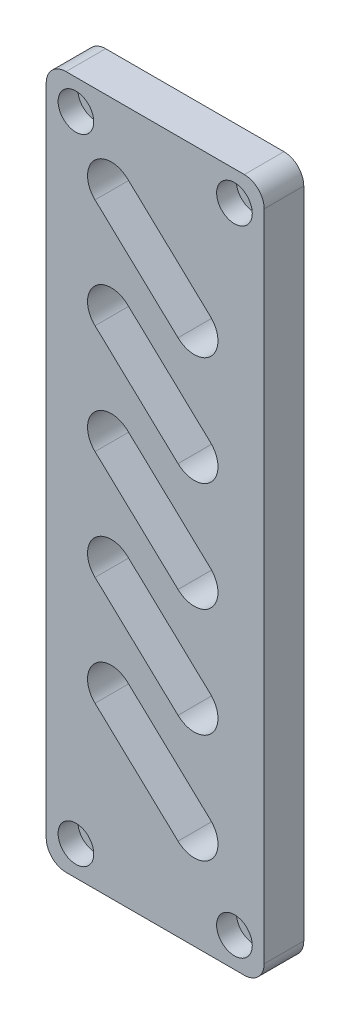
SolidWorks part; units mm, degrees
ref_plane "前视基准面" through (0, 0, 0) normal (0, 0, 1) x (1, 0, 0)
ref_plane "上视基准面" through (0, 0, 0) normal (0, 1, 0) x (1, 0, 0)
ref_plane "右视基准面" through (0, 0, 0) normal (1, 0, 0) x (0, 0, -1)
sketch "草图1" plane through (0, 0, 0) normal (0, 0, 1) x (1, 0, 0)
  line L1 (42.9443, 21.6254) -> (53.9443, 21.6254)
  line L2 (42.9443, 21.6254) -> (42.9443, -13.3746)
  line L3 (42.9443, -13.3746) -> (53.9443, -13.3746)
  line L4 (53.9443, 21.6254) -> (53.9443, -13.3746)
  point P4 (58.1842, 19.5526)
  point P6 (47.1842, -17.8474)
  dimension "D1" = 11
  dimension "D2" = 35
extrude "凸台-拉伸1" add sketch "草图1" along normal blind 2
fillet "圆角1" radius 1 4 edges at (53.9443, 21.6254, 1) (53.9443, -13.3746, 1) (42.9443, -13.3746, 1) (42.9443, 21.6254, 1)
sketch "草图2" plane through (0, 0, 0) normal (0, 0, -1) x (-1, 0, 0)
  line L0 (-53.9443, -12.3746) -> (-53.9443, 20.6254) construction
  line L1 (-52.9449, 18.5705) -> (-51.9449, 18.5705)
  line L2 (-52.9449, 18.5705) -> (-52.9449, -9.2307)
  line L3 (-52.9449, -9.2307) -> (-51.9449, -9.2307)
  line L4 (-51.9449, 18.5705) -> (-51.9449, -9.2307)
  line L5 (-42.9443, 20.6254) -> (-42.9443, -12.3746) construction
  line L6 (-44.9443, 16.6339) -> (-43.9443, 16.6339)
  line L7 (-44.9443, 16.6339) -> (-44.9443, 3.9371)
  line L8 (-44.9443, 3.9371) -> (-43.9443, 3.9371)
  line L9 (-43.9443, 16.6339) -> (-43.9443, 3.9371)
  line L10 (-43.9443, -13.3746) -> (-52.9443, -13.3746) construction
  line L11 (-51.919, 20.6254) -> (-45.191, 20.6254)
  line L12 (-51.919, 20.6254) -> (-51.919, 19.6254)
  line L13 (-51.919, 19.6254) -> (-45.191, 19.6254)
  line L14 (-45.191, 20.6254) -> (-45.191, 19.6254)
  line L15 (-51.771, -11.3746) -> (-45.174, -11.3746)
  line L16 (-51.771, -11.3746) -> (-51.771, -12.3746)
  line L17 (-51.771, -12.3746) -> (-45.174, -12.3746)
  line L18 (-45.174, -11.3746) -> (-45.174, -12.3746)
  line L19 (-52.9443, 21.6254) -> (-43.9443, 21.6254) construction
  dimension "D1" = 0.9994
  dimension "D2" = 1
  dimension "D3" = 1
  dimension "D4" = 1
  dimension "D5" = 1
  dimension "D6" = 1
  dimension "D7" = 1
  dimension "D8" = 1
extrude "凸台-拉伸2" add sketch "草图2" along normal blind 1
sketch "草图3" plane through (0, -12.3746, 0) normal (0, -1, 0) x (1, 0, 0)
  line L1 (45.174, -0.5) -> (51.8154, -0.5)
  line L2 (45.174, -0.5) -> (45.174, -1)
  line L3 (45.174, -1) -> (51.8154, -1)
  line L4 (51.8154, -0.5) -> (51.8154, -1)
  line L5 (51.771, -1) -> (45.174, -1) construction
  line L6 (51.8154, -1.0095) -> (51.8154, -0.5026) construction
  line L7 (45.174, -1) -> (45.174, 0) construction
  dimension "D1" = 0.5
extrude "凸台-拉伸3" add sketch "草图3" along normal blind 0.5
sketch "草图4" plane through (43.9443, 0, 0) normal (-1, 0, 0) x (0, 0, 1)
  line L0 (-1, 16.6339) -> (0, 16.6339) construction
  line L1 (-0.5, 16.6339) -> (-1, 16.6339)
  line L2 (-0.5, 16.6339) -> (-0.5, 3.9371)
  line L3 (-0.5, 3.9371) -> (-1, 3.9371)
  line L4 (-1, 16.6339) -> (-1, 3.9371)
  dimension "D1" = 0.5
extrude "凸台-拉伸4" add sketch "草图4" along normal blind 0.5
sketch "草图5" plane through (0, 20.6254, 0) normal (0, 1, 0) x (1, 0, 0)
  line L0 (45.191, 1) -> (45.191, 0) construction
  line L1 (45.191, 1) -> (51.919, 1)
  line L2 (45.191, 1) -> (45.191, 0.5)
  line L3 (45.191, 0.5) -> (51.919, 0.5)
  line L4 (51.919, 1) -> (51.919, 0.5)
  line L5 (45.191, 1) -> (51.919, 1) construction
  line L6 (51.919, 1) -> (51.919, 0) construction
  dimension "D1" = 0.5
extrude "凸台-拉伸5" add sketch "草图5" along normal blind 0.5
sketch "草图6" plane through (52.9449, 0, 0) normal (1, 0, 0) x (0, 0, -1)
  line L1 (1, 18.5705) -> (0.5, 18.5705)
  line L2 (1, 18.5705) -> (1, -9.2307)
  line L3 (1, -9.2307) -> (0.5, -9.2307)
  line L4 (0.5, 18.5705) -> (0.5, -9.2307)
  line L8 (1, 18.5705) -> (1, -9.2307) construction
  line L9 (1, 18.5705) -> (0, 18.5705) construction
  line L10 (1, -9.2307) -> (0, -9.2307) construction
  dimension "D1" = 0.5
extrude "凸台-拉伸6" add sketch "草图6" along normal blind 0.5
chamfer "倒角1" distance 0.5 angle 45 4 edges at (48.4947, -12.8746, -1) (53.4449, 4.6699, -1) (48.555, 21.1254, -1) (43.4443, 10.2855, -1)
sketch "草图7" plane through (0, 0, 2) normal (0, 0, 1) x (1, 0, 0)
  line L0 (46.2277, 17.6217) -> (50.4159, 13.6893) construction
  line L1 (47.0472, 18.4945) -> (51.2354, 14.5621)
  line L2 (45.4083, 16.7489) -> (49.5964, 12.8166)
  line L3 (45.4083, 11.2489) -> (49.5964, 7.3166)
  line L4 (47.0472, 12.9945) -> (51.2354, 9.0621)
  line L5 (46.2277, 12.1217) -> (50.4159, 8.1893) construction
  line L6 (45.4083, 5.7489) -> (49.5964, 1.8166)
  line L7 (47.0472, 7.4945) -> (51.2354, 3.5621)
  line L8 (46.2277, 6.6217) -> (50.4159, 2.6893) construction
  line L9 (45.4083, 0.2489) -> (49.5964, -3.6834)
  line L10 (47.0472, 1.9945) -> (51.2354, -1.9379)
  line L11 (46.2277, 1.1217) -> (50.4159, -2.8107) construction
  line L12 (45.4083, -5.2511) -> (49.5964, -9.1834)
  line L13 (47.0472, -3.5055) -> (51.2354, -7.4379)
  line L14 (46.2277, -4.3783) -> (50.4159, -8.3107) construction
  arc A0 (47.0472, 18.4945) -> (45.4083, 16.7489) centre (46.2277, 17.6217) ccw
  arc A1 (49.5964, 12.8166) -> (51.2354, 14.5621) centre (50.4159, 13.6893) ccw
  arc A2 (47.0472, 12.9945) -> (45.4083, 11.2489) centre (46.2277, 12.1217) ccw
  arc A3 (49.5964, 7.3166) -> (51.2354, 9.0621) centre (50.4159, 8.1893) ccw
  arc A4 (47.0472, 7.4945) -> (45.4083, 5.7489) centre (46.2277, 6.6217) ccw
  arc A5 (49.5964, 1.8166) -> (51.2354, 3.5621) centre (50.4159, 2.6893) ccw
  arc A6 (47.0472, 1.9945) -> (45.4083, 0.2489) centre (46.2277, 1.1217) ccw
  arc A7 (49.5964, -3.6834) -> (51.2354, -1.9379) centre (50.4159, -2.8107) ccw
  arc A8 (47.0472, -3.5055) -> (45.4083, -5.2511) centre (46.2277, -4.3783) ccw
  arc A9 (49.5964, -9.1834) -> (51.2354, -7.4379) centre (50.4159, -8.3107) ccw
  point P2 (48.3218, 15.6555)
  point P7 (0, 0)
  point P11 (48.3218, 10.1555)
  point P18 (48.3218, 4.6555)
  point P25 (48.3218, -0.8445)
  point P32 (48.3218, -6.3445)
  dimension "D1" = 5
extrude "切除-拉伸1" cut sketch "草图7" against normal up to next
sketch "草图8" plane through (0, 0, 2) normal (0, 0, 1) x (1, 0, 0)
  line L0 (42.9443, 20.6254) -> (42.9443, -12.3746) construction
  line L3 (43.9443, -13.3746) -> (52.9443, -13.3746) construction
  line L4 (53.9443, -12.3746) -> (53.9443, 20.6254) construction
  line L6 (52.9443, 21.6254) -> (43.9443, 21.6254) construction
  circle A0 centre (44.4443, 20.1254) radius 0.9
  circle A1 centre (52.4443, 20.1254) radius 0.9
  circle A2 centre (44.4443, -11.8746) radius 0.9
  circle A3 centre (52.4443, -11.8746) radius 0.9
  point P9 (0, 0)
  point P10 (0, 0)
  point P11 (0, 0)
  point P12 (0, 0)
  point P15 (0, 0)
  point P17 (41.4794, -14.3405)
  point P18 (43.2571, -14.3405)
  point P20 (0, 0)
  point P21 (0, 0)
  point P24 (0, 0)
  point P26 (46.4125, 19.6595)
  point P28 (0, 0)
  point P29 (0, 0)
  point P30 (0, 0)
  dimension "D1" = 1.8
  dimension "D2" = 1.5
  dimension "D3" = 1.5
  dimension "D4" = 1.5
  dimension "D5" = 1.5
extrude "切除-拉伸2" cut sketch "草图8" against normal blind 1
sketch "草图9" plane through (0, 0, 1) normal (0, 0, 1) x (1, 0, 0)
  circle A0 centre (44.4443, 20.1254) radius 0.5
  circle A1 centre (52.4443, 20.1254) radius 0.5
  circle A2 centre (52.4443, -11.8746) radius 0.5
  circle A3 centre (44.4443, -11.8746) radius 0.5
  dimension "D1" = 1
extrude "切除-拉伸3" cut sketch "草图9" against normal blind 1
